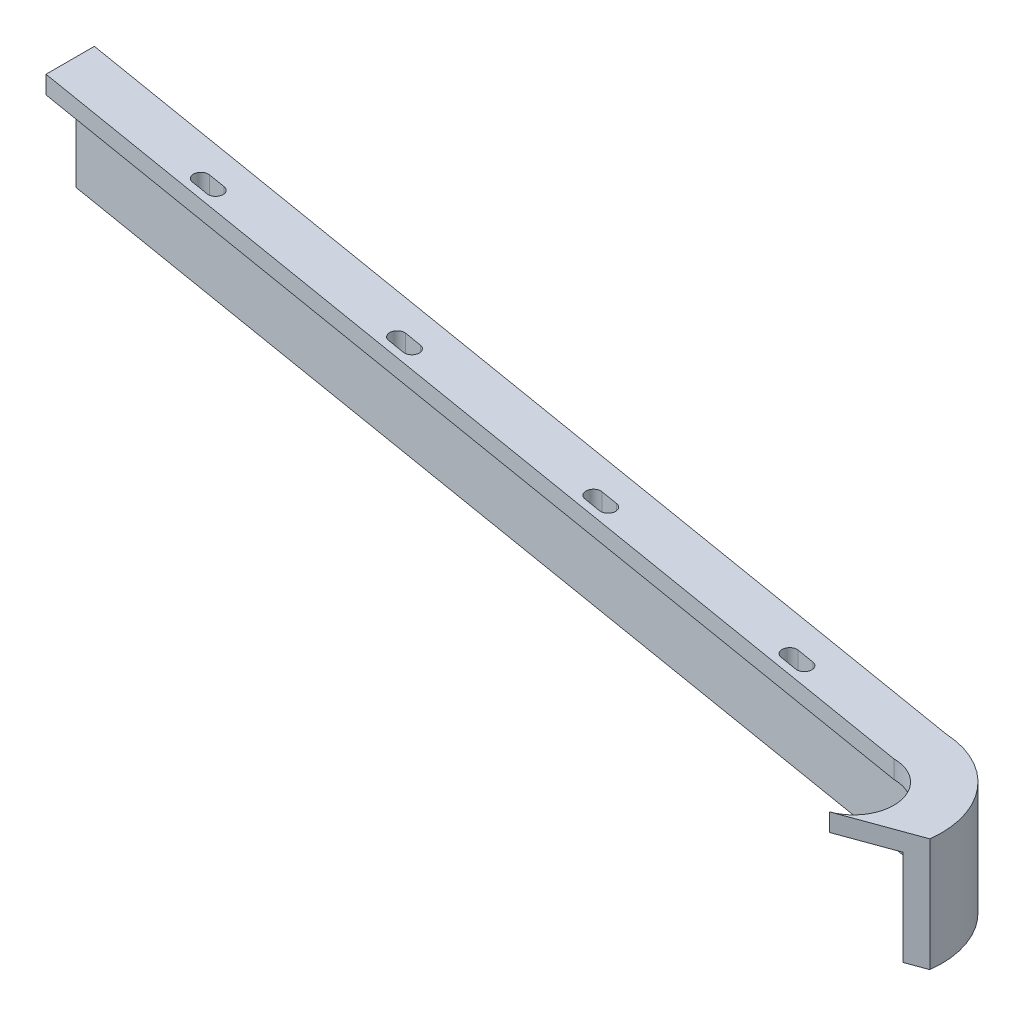
SolidWorks part; units mm, degrees
ref_plane "前视基准面" through (0, 0, 0) normal (0, 0, 1) x (1, 0, 0)
ref_plane "上视基准面" through (0, 0, 0) normal (0, 1, 0) x (1, 0, 0)
ref_plane "右视基准面" through (0, 0, 0) normal (1, 0, 0) x (0, 0, -1)
sketch "草图1" plane through (0, 0, 0) normal (0, 1, 0) x (1, 0, 0)
  line L1 (-17.5, -27.5) -> (17.5, -27.5)
  line L2 (-17.5, -27.5) -> (-17.5, 27.5)
  line L3 (-17.5, 27.5) -> (17.5, 27.5)
  line L4 (17.5, -27.5) -> (17.5, 27.5)
  line L5 (-17.5, -27.5) -> (17.5, 27.5) construction
  line L6 (-17.5, 27.5) -> (17.5, -27.5) construction
  point P0 (0, 0)
  dimension "D1" = 55
  dimension "D2" = 35
extrude "凸台-拉伸1" add sketch "草图1" along normal blind 1
sketch "草图2" plane through (0, 1, 0) normal (0, 1, 0) x (1, 0, 0)
  line L0 (-105.917, 0) -> (-62.25, 0) construction
  line L1 (106.75, 2.25) -> (121.75, 2.25)
  line L2 (-31.4474, 57.1013) -> (151.75, 26.6691)
  line L4 (124.0586, 2.6571) -> (154.0586, 13.5762)
  line L5 (-60.1618, 23.6059) -> (-42.6093, 52.0296)
  line L6 (121.75, 2.25) -> (121.75, 9) construction
  line L7 (121.75, -2.25) -> (121.75, -9) construction
  line L8 (-60.1618, -23.6059) -> (-42.6093, -52.0296)
  line L9 (124.0586, -2.6571) -> (154.0586, -13.5762)
  line L10 (121.75, -9) -> (128.5, -9)
  line L11 (-31.4474, -57.1013) -> (151.75, -26.6691)
  line L12 (106.75, -2.25) -> (121.75, -2.25)
  line L13 (-62.25, 16.25) -> (-62.25, -16.25)
  line L14 (106.75, 2.25) -> (106.75, -2.25)
  line L15 (106.75, 0) -> (124.0666, 0) construction
  arc A0 (-60.1618, 23.6059) -> (-62.25, 16.25) centre (-48.25, 16.25) ccw
  arc A1 (-31.4474, 57.1013) -> (-42.6093, 52.0296) centre (-33.25, 46.25) ccw
  arc A2 (121.75, 2.25) -> (124.0586, 2.6571) centre (121.75, 9) ccw
  arc A3 (154.0586, 13.5762) -> (151.75, 26.6691) centre (151.75, 19.9191) ccw
  arc A4 (154.0586, -13.5762) -> (151.75, -26.6691) centre (151.75, -19.9191) cw
  arc A5 (121.75, -2.25) -> (128.5, -9) centre (121.75, -9) cw
  arc A6 (-31.4474, -57.1013) -> (-42.6093, -52.0296) centre (-33.25, -46.25) cw
  arc A7 (-60.1618, -23.6059) -> (-62.25, -16.25) centre (-48.25, -16.25) cw
  line M10 (17.5, -27.5) -> (17.5, 27.5)
  line M11 (17.5, 27.5) -> (-17.5, 27.5)
  line M12 (-17.5, 27.5) -> (-17.5, -27.5)
  line M13 (-17.5, -27.5) -> (17.5, -27.5)
  dimension "D2" = 28
  dimension "D3" = 48.25
  dimension "D4" = 22
  dimension "D5" = 15
  dimension "D7" = 13.5
  dimension "D10" = 13.5
  dimension "D11" = 30
  dimension "D1" = 2.25
  dimension "D8" = 20
  dimension "D9" = 30
  dimension "D12" = 15
extrude "凸台-拉伸2" add sketch "草图2" along normal blind 3 contours A7 L8 A6 L11 A4 L9 A5 L12 L14 L1 A2 L4 A3 L2 A1 L5 A0 L13 | M13 M10 M11 M12 region at (37.3678, 1, 0) region at (0, 1, 0)
sketch "草图3" plane through (0, 4, 0) normal (0, 1, 0) x (1, 0, 0)
  circle A0 centre (-48.25, 16.25) radius 5
  circle A1 centre (-48.25, -16.25) radius 5
  circle A2 centre (-33.25, 46.25) radius 6.6982
  circle A3 centre (151.75, 19.9191) radius 2.5794
  circle A4 centre (121.75, 9) radius 2.5794
  circle A5 centre (121.75, -9) radius 2.5794
  circle A6 centre (151.75, -19.9191) radius 2.5794
  circle A7 centre (-33.25, -46.25) radius 6.6982
  dimension "D1" = 10
extrude "切除-拉伸1" cut sketch "草图3" against normal through all contours A0 | A1 region at (-48.25, 4, -16.25)
sketch "草图4" plane through (0, 4, 0) normal (0, 1, 0) x (1, 0, 0)
  circle A0 centre (-33.25, 46.25) radius 4
  circle A1 centre (-33.25, -46.25) radius 4
  dimension "D1" = 8
  dimension "D2" = 8
extrude "切除-拉伸2" cut sketch "草图4" against normal blind 2
sketch "草图5" plane through (0, 4, 0) normal (0, 1, 0) x (1, 0, 0)
  circle A0 centre (121.75, 9) radius 2
  circle A1 centre (121.75, -9) radius 2
  circle A2 centre (151.75, 19.9191) radius 2
  circle A3 centre (151.75, -19.9191) radius 2
  dimension "D1" = 4
extrude "切除-拉伸3" cut sketch "草图5" against normal blind 2
sketch "草图8" plane through (0, 1, 0) normal (0, -1, 0) x (1, 0, 0)
  line L1 (-39.75, -26.25) -> (-26.75, -26.25)
  line L2 (-39.75, -26.25) -> (-39.75, -66.25)
  line L3 (-39.75, -66.25) -> (-26.75, -66.25)
  line L4 (-26.75, -26.25) -> (-26.75, -66.25)
  line L5 (-39.75, -26.25) -> (-26.75, -66.25) construction
  line L6 (-39.75, -66.25) -> (-26.75, -26.25) construction
  line L16 (124.0586, 2.6571) -> (154.0586, 13.5762)
  line L17 (151.75, 26.6691) -> (-31.4474, 57.1013)
  line L18 (-42.6093, 52.0296) -> (-60.1618, 23.6059)
  line L19 (-62.25, 16.25) -> (-62.25, -16.25)
  line L20 (-60.1618, -23.6059) -> (-42.6093, -52.0296)
  line L21 (-31.4474, -57.1013) -> (151.75, -26.6691)
  line L22 (154.0586, -13.5762) -> (124.0586, -2.6571)
  line L23 (121.75, -2.25) -> (106.75, -2.25)
  line L24 (106.75, -2.25) -> (106.75, 2.25)
  line L25 (106.75, 2.25) -> (121.75, 2.25)
  line L26 (124.0586, 2.6571) -> (154.0586, 13.5762)
  line L27 (151.75, 26.6691) -> (-31.4474, 57.1013)
  line L28 (-42.6093, 52.0296) -> (-60.1618, 23.6059)
  line L31 (-31.4474, -57.1013) -> (151.75, -26.6691)
  line L32 (154.0586, -13.5762) -> (124.0586, -2.6571)
  line L33 (121.75, -2.25) -> (106.75, -2.25)
  line L34 (106.75, -2.25) -> (106.75, 2.25)
  line L35 (106.75, 2.25) -> (121.75, 2.25)
  arc A8 (154.0586, 13.5762) -> (151.75, 26.6691) centre (151.75, 19.9191) ccw
  arc A9 (-31.4474, 57.1013) -> (-42.6093, 52.0296) centre (-33.25, 46.25) ccw
  arc A10 (-60.1618, 23.6059) -> (-62.25, 16.25) centre (-48.25, 16.25) ccw
  arc A11 (-62.25, -16.25) -> (-60.1618, -23.6059) centre (-48.25, -16.25) ccw
  arc A12 (-42.6093, -52.0296) -> (-31.4474, -57.1013) centre (-33.25, -46.25) ccw
  arc A13 (151.75, -26.6691) -> (154.0586, -13.5762) centre (151.75, -19.9191) ccw
  arc A14 (124.0586, -2.6571) -> (121.75, -2.25) centre (121.75, -9) ccw
  arc A15 (121.75, 2.25) -> (124.0586, 2.6571) centre (121.75, 9) ccw
  arc A16 (154.0586, 13.5762) -> (151.75, 26.6691) centre (151.75, 19.9191) ccw
  arc A17 (-31.4474, 57.1013) -> (-42.6093, 52.0296) centre (-33.25, 46.25) ccw
  arc A18 (-60.1618, 23.6059) -> (-62.25, 16.25) centre (-48.25, 16.25) ccw
  arc A19 (-62.25, -16.25) -> (-60.1618, -23.6059) centre (-48.25, -16.25) ccw
  arc A20 (-42.6093, -52.0296) -> (-31.4474, -57.1013) centre (-33.25, -46.25) ccw
  arc A21 (151.75, -26.6691) -> (154.0586, -13.5762) centre (151.75, -19.9191) ccw
  arc A22 (124.0586, -2.6571) -> (121.75, -2.25) centre (121.75, -9) ccw
  arc A23 (121.75, 2.25) -> (124.0586, 2.6571) centre (121.75, 9) ccw
  point P0 (-33.25, -46.25)
  arc M32 (-42.6093, -52.0296) -> (-31.4474, -57.1013) centre (-33.25, -46.25) ccw
  line M33 (-31.4474, -57.1013) -> (151.75, -26.6691)
  dimension "D1" = 13
  dimension "D2" = 40
  dimension "D3" = 0
extrude "凸台-拉伸3" add sketch "草图8" along normal blind 7 contours L4 L1 L2 M32 M33 region at (-33.2258, 1, -41.4837)
mirror "镜向1" about plane through (0, 0, 0) normal (0, 0, 1) of "凸台-拉伸3"
sketch "草图9" plane through (0, -6, 0) normal (0, -1, 0) x (1, 0, 0)
  line L0 (-39.75, -26.25) -> (-26.75, -26.25) construction
  line L2 (-38.25, -53.75) -> (-38.25, -27.75)
  line L3 (-38.25, -27.75) -> (-28.25, -27.75)
  line L4 (-28.25, -53.75) -> (-28.25, -27.75)
  line L5 (-35.5448, -54.7408) -> (-28.25, -27.75) construction
  line L6 (-38.25, -27.75) -> (-31.223, -53.75) construction
  line L8 (-28.25, -53.75) -> (-38.25, -53.75)
  point P0 (-33.25, -46.25)
  dimension "D1" = 10
  dimension "D2" = 1.5
  dimension "D3" = 26
extrude "切除-拉伸4" cut sketch "草图9" against normal through all from offset 1.5 offset against normal yes
mirror "镜向2" about plane through (0, 0, 0) normal (0, 0, 1) of "切除-拉伸4"
sketch "草图10" plane through (0, 0, -53.75) normal (0, 0, 1) x (1, 0, 0)
  line L4 (-38.25, -4.5) -> (-28.25, -4.5)
  line L5 (-28.25, -4.5) -> (-28.25, 4)
  line L6 (-28.25, 4) -> (-38.25, 4)
  line L7 (-38.25, 4) -> (-38.25, -4.5)
  line L8 (-38.25, -4.5) -> (-28.25, -4.5)
  line L9 (-28.25, -4.5) -> (-28.25, 4)
  line L10 (-28.25, 4) -> (-38.25, 4)
  line L11 (-38.25, 4) -> (-38.25, -4.5)
  circle A0 centre (-33.25, -1.5) radius 1.5
  dimension "D2" = 3
  dimension "D3" = 3
  dimension "D1" = 0
extrude "切除-拉伸5" cut sketch "草图10" against normal through all contours A0 region at (-33.25, -1.5, -53.75)
mirror "镜向3" about plane through (0, 0, 0) normal (0, 0, 1) of "切除-拉伸5"
sketch "草图12" plane through (0, 4, 0) normal (0, 1, 0) x (1, 0, 0)
  line L3 (152.5362, 34.6481) -> (-30.1364, 64.9932)
  line L5 (-42.6093, 52.0296) -> (-60.1618, 23.6059) construction
  line L6 (124.0586, 2.6571) -> (154.0586, 13.5762) construction
  line L10 (154.0586, -13.5762) -> (124.0586, -2.6571)
  line L11 (121.75, -2.25) -> (106.75, -2.25)
  line L12 (106.75, -2.25) -> (106.75, 2.25)
  line L13 (106.75, 2.25) -> (121.75, 2.25)
  line L14 (124.0586, 2.6571) -> (154.0586, 13.5762)
  line L15 (151.75, 26.6691) -> (-31.4474, 57.1013)
  line L16 (-42.6093, 52.0296) -> (-60.1618, 23.6059)
  line L17 (-62.25, 16.25) -> (-62.25, -16.25)
  line L18 (-60.1618, -23.6059) -> (-42.6093, -52.0296)
  line L19 (-31.4474, -57.1013) -> (151.75, -26.6691)
  line L23 (-62.25, 2.25) -> (121.75, 2.25)
  line L24 (124.0586, 2.6571) -> (166.3826, 18.0617)
  line L26 (-34.4695, 65.2108) -> (-60.1618, 23.6059)
  line L27 (-62.25, 16.25) -> (-62.25, 2.25)
  line L30 (-49.416, 56.233) -> (-66.9685, 27.8093) construction
  line L31 (-70.25, 16.25) -> (-70.25, -5.75) construction
  line L32 (-70.25, -5.75) -> (121.75, -5.75) construction
  line L33 (126.7948, -4.8605) -> (156.7948, 6.0586) construction
  line L34 (151.75, 26.6691) -> (-31.4474, 57.1013) construction
  arc A1 (166.3826, 18.0617) -> (152.5362, 34.6481) centre (151.75, 19.9191) ccw
  arc A2 (-30.1364, 64.9932) -> (-34.4695, 65.2108) centre (-33.25, 46.25) ccw
  arc A4 (-30.1364, 64.9932) -> (-49.416, 56.233) centre (-33.25, 46.25) ccw construction
  arc A5 (156.7948, 6.0586) -> (152.5362, 34.6481) centre (151.75, 19.9191) ccw construction
  arc A8 (124.0586, -2.6571) -> (121.75, -2.25) centre (121.75, -9) ccw
  arc A9 (121.75, 2.25) -> (124.0586, 2.6571) centre (121.75, 9) ccw
  arc A10 (154.0586, 13.5762) -> (151.75, 26.6691) centre (151.75, 19.9191) ccw
  arc A11 (-31.4474, 57.1013) -> (-42.6093, 52.0296) centre (-33.25, 46.25) ccw
  arc A12 (-60.1618, 23.6059) -> (-62.25, 16.25) centre (-48.25, 16.25) ccw
  arc A13 (-62.25, -16.25) -> (-60.1618, -23.6059) centre (-48.25, -16.25) ccw
  arc A14 (-42.6093, -52.0296) -> (-31.4474, -57.1013) centre (-33.25, -46.25) ccw
  arc A15 (151.75, -26.6691) -> (154.0586, -13.5762) centre (151.75, -19.9191) ccw
  arc A17 (121.75, 2.25) -> (124.0586, 2.6571) centre (121.75, 9) ccw
  arc A20 (-60.1618, 23.6059) -> (-62.25, 16.25) centre (-48.25, 16.25) ccw
  arc A24 (-66.9685, 27.8093) -> (-70.25, 16.25) centre (-48.25, 16.25) ccw construction
  arc A25 (121.75, -5.75) -> (126.7948, -4.8605) centre (121.75, 9) ccw construction
  arc A26 (-31.4474, 57.1013) -> (-42.6093, 52.0296) centre (-33.25, 46.25) ccw construction
  arc A27 (154.0586, 13.5762) -> (151.75, 26.6691) centre (151.75, 19.9191) ccw construction
  dimension "D1" = 0
  dimension "D2" = 8
extrude "凸台-拉伸4" add sketch "草图12" along normal blind 3
sketch "草图13" plane through (0, 4, 0) normal (0, -1, 0) x (1, 0, 0)
  line L1 (-119.1699, 86.8947) -> (214.8426, 86.8947)
  line L2 (-119.1699, 86.8947) -> (-119.1699, -74.5615)
  line L3 (-119.1699, -74.5615) -> (214.8426, -74.5615)
  line L4 (214.8426, 86.8947) -> (214.8426, -74.5615)
  line L5 (-119.1699, 86.8947) -> (214.8426, -74.5615) construction
  line L6 (-119.1699, -74.5615) -> (214.8426, 86.8947) construction
  point P0 (47.8363, 6.1666)
extrude "切除-拉伸6" cut sketch "草图13" along normal blind 10
sketch "草图14" plane through (0, 4, 0) normal (0, -1, 0) x (1, 0, 0)
  circle A0 centre (151.75, -19.9191) radius 3.5
  circle A1 centre (121.75, -9) radius 3.5
  dimension "D2" = 7
  dimension "D3" = 7
extrude "切除-拉伸7" cut sketch "草图14" against normal blind 2.5
sketch "草图15" plane through (0, 4, 0) normal (0, -1, 0) x (1, 0, 0)
  circle A0 centre (-48.25, -16.25) radius 5
  dimension "D1" = 10
extrude "切除-拉伸8" cut sketch "草图15" against normal through all
sketch "草图17" plane through (0, 4, 0) normal (0, -1, 0) x (1, 0, 0)
  line L0 (-30.6281, -62.0337) -> (152.2188, -31.6598)
  line L1 (-34.4695, -65.2108) -> (-36.5044, -61.9155)
  line L3 (166.3826, -18.0617) -> (163.0963, -16.8656)
  line L5 (166.3826, -18.0617) -> (124.0586, -2.6571)
  line L6 (121.75, -2.25) -> (-62.25, -2.25)
  line L7 (-62.25, -2.25) -> (-62.25, -16.25)
  line L8 (-60.1618, -23.6059) -> (-34.4695, -65.2108)
  line L9 (-30.1364, -64.9932) -> (152.5362, -34.6481)
  line L14 (-30.1364, -64.9932) -> (152.5362, -34.6481)
  arc A0 (-36.5044, -61.9155) -> (-30.6281, -62.0337) centre (-33.25, -46.25) ccw
  arc A1 (152.2188, -31.6598) -> (163.0963, -16.8656) centre (151.75, -19.9191) ccw
  arc A2 (-34.2769, -62.217) -> (-30.6281, -62.0337) centre (-33.25, -46.25) ccw construction
  arc A3 (152.2188, -31.6598) -> (163.4065, -18.4395) centre (151.75, -19.9191) ccw construction
  arc A4 (124.0586, -2.6571) -> (121.75, -2.25) centre (121.75, -9) ccw
  arc A5 (-62.25, -16.25) -> (-60.1618, -23.6059) centre (-48.25, -16.25) ccw
  arc A6 (-34.4695, -65.2108) -> (-30.1364, -64.9932) centre (-33.25, -46.25) ccw
  arc A7 (152.5362, -34.6481) -> (166.3826, -18.0617) centre (151.75, -19.9191) ccw
  arc A10 (-34.4695, -65.2108) -> (-30.1364, -64.9932) centre (-33.25, -46.25) ccw
  arc A11 (152.5362, -34.6481) -> (166.3826, -18.0617) centre (151.75, -19.9191) ccw
  dimension "D1" = 0
  dimension "D2" = 3
extrude "凸台-拉伸5" add sketch "草图17" along normal blind 16
sketch "草图18" plane through (0, 7, 0) normal (0, 1, 0) x (1, 0, 0)
  line L1 (-39.75, 26.25) -> (-26.75, 26.25)
  line L2 (-39.75, 26.25) -> (-39.75, 56.6598)
  line L4 (-26.75, 26.25) -> (-26.75, 64.4306)
  line L5 (-39.75, 26.25) -> (-27.311, 64.5238) construction
  line L6 (-37.7079, 59.9667) -> (-26.75, 26.25) construction
  line L11 (-62.25, 16.25) -> (-62.25, 2.25)
  line L12 (-62.25, 2.25) -> (121.75, 2.25)
  line L13 (124.0586, 2.6571) -> (166.3826, 18.0617)
  line L14 (152.5362, 34.6481) -> (-30.1364, 64.9932)
  line L15 (-34.4695, 65.2108) -> (-60.1618, 23.6059)
  line L19 (-26.75, 64.4306) -> (-30.1364, 64.9932)
  line L20 (-34.4695, 65.2108) -> (-39.75, 56.6598)
  arc A0 (-30.1364, 64.9932) -> (-34.4695, 65.2108) centre (-33.25, 46.25) ccw construction
  arc A1 (-30.1364, 64.9932) -> (-34.4695, 65.2108) centre (-33.25, 46.25) ccw
  arc A6 (121.75, 2.25) -> (124.0586, 2.6571) centre (121.75, 9) ccw
  arc A7 (166.3826, 18.0617) -> (152.5362, 34.6481) centre (151.75, 19.9191) ccw
  arc A8 (-30.1364, 64.9932) -> (-34.4695, 65.2108) centre (-33.25, 46.25) ccw
  arc A9 (-60.1618, 23.6059) -> (-62.25, 16.25) centre (-48.25, 16.25) ccw
  arc A10 (121.75, 2.25) -> (124.0586, 2.6571) centre (121.75, 9) ccw
  arc A12 (-30.1364, 64.9932) -> (-34.4695, 65.2108) centre (-33.25, 46.25) ccw
  line M18 (152.5362, 34.6481) -> (-30.1364, 64.9932)
  arc M19 (-30.1364, 64.9932) -> (-34.4695, 65.2108) centre (-33.25, 46.25) ccw
  line M20 (-34.4695, 65.2108) -> (-60.1618, 23.6059)
  dimension "D3" = 0
extrude "凸台-拉伸6" add sketch "草图18" along normal blind 7 contours L1 L4 L2 M18 M19 M20 region at (-33.0469, 7, -44.8798)
sketch "草图19" plane through (0, 14, 0) normal (0, 1, 0) x (1, 0, 0)
  line L5 (-38.25, 53.75) -> (-28.25, 53.75)
  line L8 (-38.25, 27.75) -> (-28.25, 27.75)
  line L9 (-28.25, 64.75) -> (-28.25, 64.6798)
  line L10 (-39.75, 26.25) -> (-26.75, 26.25)
  line L11 (-26.75, 26.25) -> (-26.75, 64.4306)
  line L12 (-26.75, 64.4306) -> (-30.1364, 64.9932)
  line L13 (-34.4695, 65.2108) -> (-39.75, 56.6598)
  line L14 (-39.75, 56.6598) -> (-39.75, 26.25)
  line L17 (-26.75, 64.4306) -> (-28.6727, 64.75)
  line L18 (-34.4695, 65.2108) -> (-34.754, 64.75)
  line L21 (-38.25, 27.75) -> (-31.223, 53.75) construction
  line L22 (-38.25, 53.75) -> (-38.25, 27.75)
  line L23 (-35.277, 53.75) -> (-28.25, 27.75) construction
  line L24 (-28.2682, 64.6828) -> (-28.25, 64.75) construction
  line L25 (-28.25, 53.75) -> (-28.25, 27.75)
  line L27 (-28.6727, 64.75) -> (-28.25, 64.75)
  arc A2 (-30.1364, 64.9932) -> (-34.4695, 65.2108) centre (-33.25, 46.25) ccw
  dimension "D2" = 10
  dimension "D4" = 26
  dimension "D1" = 0
extrude "切除-拉伸9" cut sketch "草图19" against normal through all from offset 1.5 contours L25 L5 L22 L8 region at (-33.25, 14, -40.75) offset against normal yes
sketch "草图20" plane through (0, 0, -53.75) normal (0, 0, 1) x (1, 0, 0)
  line L4 (-38.25, 4) -> (-28.25, 4)
  line L5 (-28.25, 4) -> (-28.25, 12.5)
  line L6 (-28.25, 12.5) -> (-38.25, 12.5)
  line L7 (-38.25, 12.5) -> (-38.25, 4)
  line L8 (-38.25, 4) -> (-28.25, 4)
  line L9 (-28.25, 4) -> (-28.25, 12.5)
  line L10 (-28.25, 12.5) -> (-38.25, 12.5)
  line L11 (-38.25, 12.5) -> (-38.25, 4)
  circle A0 centre (-33.25, 9.5) radius 1.5
  dimension "D2" = 3
  dimension "D3" = 3
  dimension "D1" = 0
extrude "切除-拉伸10" cut sketch "草图20" against normal through all contours A0 region at (-33.25, 9.5, -53.75)
thread "螺纹线1" pitch 0.6 method cut profile "螺纹线轮廓1" start angle 0, offset 0, length 15, pitch 0.6, diameter 3
ref_plane "基准面1" through (-34.75, 9.5, -53.75) normal (0, -1, 0) x (-1, 0, 0)
sketch "螺纹线轮廓1" plane through (-34.75, 9.5, -53.75) normal (0, -1, 0) x (-1, 0, 0)
  line L0 (0, 0) -> (0, 0.6) construction
  line L1 (0, 0) -> (0.3248, 0.1875)
  line L2 (0.3248, 0.1875) -> (0.3248, 0.2625)
  line L3 (0.3248, 0.2625) -> (0, 0.45)
  line L4 (0.3248, 0.225) -> (0, 0.225) construction
  line L11 (0, 0) -> (0, 0.45)
  point P2 (0, 0)
  dimension "Pitch" = 0.6
  dimension "Profile_Angle" = 60
  dimension "Profile_Land" = 0.075
  dimension "Profile_Height" = 0.3248
sketch "草图21" plane through (0, 14, 0) normal (0, 1, 0) x (1, 0, 0)
  line L0 (-38.25, 27.75) -> (-28.25, 27.75) construction
  line L1 (-39.75, 27.75) -> (-26.75, 27.75)
  line L5 (-39.75, 26.25) -> (-26.75, 26.25)
  line L6 (-26.75, 26.25) -> (-26.75, 64.4306)
  line L7 (-26.75, 64.4306) -> (-30.1364, 64.9932)
  line L8 (-34.4695, 65.2108) -> (-39.75, 56.6598)
  line L9 (-39.75, 56.6598) -> (-39.75, 26.25)
  line L11 (-26.75, 27.75) -> (-26.75, 64.4306)
  line L12 (-26.75, 64.4306) -> (-30.1364, 64.9932)
  line L13 (-34.4695, 65.2108) -> (-39.75, 56.6598)
  line L14 (-39.75, 56.6598) -> (-39.75, 27.75)
  arc A1 (-30.1364, 64.9932) -> (-34.4695, 65.2108) centre (-33.25, 46.25) ccw
  arc A2 (-30.1364, 64.9932) -> (-34.4695, 65.2108) centre (-33.25, 46.25) ccw
  dimension "D1" = 0
extrude "切除-拉伸11" cut sketch "草图21" against normal through all
sketch "草图22" plane through (0, 14, 0) normal (0, 1, 0) x (1, 0, 0)
  line L4 (-26.75, 27.75) -> (-39.75, 27.75)
  line L5 (-39.75, 27.75) -> (-39.75, 26.25)
  line L6 (-39.75, 26.25) -> (-26.75, 26.25)
  line L7 (-26.75, 26.25) -> (-26.75, 27.75)
  line L8 (-26.75, 27.75) -> (-39.75, 27.75)
  line L9 (-39.75, 27.75) -> (-39.75, 26.25)
  line L10 (-39.75, 26.25) -> (-26.75, 26.25)
  line L11 (-26.75, 26.25) -> (-26.75, 27.75)
  dimension "D1" = 0
extrude "切除-拉伸12" cut sketch "草图22" against normal up to surface (7 mm away) up to face at (-48.25, 7, -21.25)
sketch "草图23" plane through (0, 7, 0) normal (0, 1, 0) x (1, 0, 0)
  line L0 (-45.75, 27.75) -> (-20.75, 27.75)
  line L1 (-20.75, 27.75) -> (-18.75, 27.75)
  line L2 (-18.75, 63.1017) -> (-18.75, 2.25)
  line L8 (-26.75, 64.4306) -> (-26.75, 27.75)
  line L9 (-26.75, 27.75) -> (-39.75, 27.75)
  line L10 (-39.75, 27.75) -> (-39.75, 56.6598)
  line L11 (-39.75, 56.6598) -> (-60.1618, 23.6059)
  line L12 (-62.25, 16.25) -> (-62.25, 2.25)
  line L13 (-62.25, 2.25) -> (121.75, 2.25)
  line L14 (124.0586, 2.6571) -> (166.3826, 18.0617)
  line L15 (152.5362, 34.6481) -> (-26.75, 64.4306)
  line L16 (-26.75, 64.4306) -> (-26.75, 27.75)
  line L17 (-26.75, 27.75) -> (-39.75, 27.75)
  line L18 (-39.75, 27.75) -> (-39.75, 56.6598)
  line L19 (-39.75, 56.6598) -> (-60.1618, 23.6059)
  line L20 (-62.25, 16.25) -> (-62.25, 2.25)
  line L21 (-62.25, 2.25) -> (-18.75, 2.25)
  line L23 (-18.75, 63.1017) -> (-26.75, 64.4306)
  circle A0 centre (-48.25, 16.25) radius 5 construction
  circle A1 centre (-48.25, 16.25) radius 5
  arc A3 (-60.1618, 23.6059) -> (-62.25, 16.25) centre (-48.25, 16.25) ccw
  arc A4 (121.75, 2.25) -> (124.0586, 2.6571) centre (121.75, 9) ccw
  arc A5 (166.3826, 18.0617) -> (152.5362, 34.6481) centre (151.75, 19.9191) ccw
  arc A6 (-60.1618, 23.6059) -> (-62.25, 16.25) centre (-48.25, 16.25) ccw
  point P13 (-33.25, 27.75)
  line M14 (-26.75, 64.4306) -> (-26.75, 27.75)
  line M15 (-26.75, 27.75) -> (-39.75, 27.75)
  line M16 (-39.75, 27.75) -> (-39.75, 56.6598)
  line M17 (-39.75, 56.6598) -> (-60.1618, 23.6059)
  arc M18 (-60.1618, 23.6059) -> (-62.25, 16.25) centre (-48.25, 16.25) ccw
  line M19 (-62.25, 16.25) -> (-62.25, 2.25)
  line M20 (-62.25, 2.25) -> (121.75, 2.25)
  line M24 (152.5362, 34.6481) -> (-26.75, 64.4306)
  circle M25 centre (-48.25, 16.25) radius 5
  dimension "D2" = 25
  dimension "D3" = 2
  dimension "D1" = 0
extrude "凸台-拉伸7" add sketch "草图23" along normal blind 2 contours L2 L1 L0 M15 M16 M17 M18 M19 M20 M25 | L2 L0 L1 M24 M14 region at (-40.7754, 7, -19.3253) region at (-22.7746, 7, -45.7601)
sketch "草图24" plane through (0, 9, 0) normal (0, 1, 0) x (1, 0, 0)
  line L0 (-45.75, 27.75) -> (-20.75, 27.75)
  line L1 (-45.75, 27.75) -> (-45.75, 46.9437)
  line L2 (-39.75, 56.6598) -> (-60.1618, 23.6059) construction
  line L3 (-20.75, 27.75) -> (-20.75, 86.4202)
  line L4 (-20.75, 86.4202) -> (-45.75, 86.4202)
  line L5 (-45.75, 86.4202) -> (-45.75, 46.0349)
  point P3 (-33.25, 27.75)
  line M3 (-39.75, 27.75) -> (-39.75, 56.6598)
  line M4 (-39.75, 56.6598) -> (-60.1618, 23.6059)
  line M9 (-18.75, 63.1017) -> (-26.75, 64.4306)
  line M10 (-26.75, 64.4306) -> (-26.75, 27.75)
  dimension "D1" = 25
extrude "切除-拉伸15" cut sketch "草图24" against normal through all from offset 3 contours L1 L0 M3 M4 | L0 L3 M9 M10 region at (-42.548, 9, -39.9394) region at (-23.7638, 9, -45.8423) offset against normal yes
sketch "草图25" plane through (0, 4, 0) normal (0, -1, 0) x (1, 0, 0)
  circle A0 centre (-48.25, -16.25) radius 7.5
  dimension "D1" = 15
extrude "切除-拉伸16" cut sketch "草图25" against normal blind 4
sketch "草图26" plane through (0, 7, 0) normal (0, 1, 0) x (1, 0, 0)
  line L0 (-48.25, 16.25) -> (51.3855, 16.25)
  line L1 (1.75, 16.25) -> (5.75, 16.25) construction
  line L2 (1.75, 18) -> (5.75, 18)
  line L3 (1.75, 14.5) -> (5.75, 14.5)
  line L4 (41.75, 16.25) -> (45.75, 16.25) construction
  line L5 (41.75, 18) -> (45.75, 18)
  line L6 (41.75, 14.5) -> (45.75, 14.5)
  line L7 (81.75, 16.25) -> (85.75, 16.25) construction
  line L8 (81.75, 18) -> (85.75, 18)
  line L9 (81.75, 14.5) -> (85.75, 14.5)
  line L10 (1.75, 31.25) -> (1.75, 35.25) construction
  line L11 (0, 31.25) -> (0, 35.25)
  line L12 (3.5, 31.25) -> (3.5, 35.25)
  arc A0 (1.75, 18) -> (1.75, 14.5) centre (1.75, 16.25) ccw
  arc A1 (5.75, 14.5) -> (5.75, 18) centre (5.75, 16.25) ccw
  arc A2 (41.75, 18) -> (41.75, 14.5) centre (41.75, 16.25) ccw
  arc A3 (45.75, 14.5) -> (45.75, 18) centre (45.75, 16.25) ccw
  arc A4 (81.75, 18) -> (81.75, 14.5) centre (81.75, 16.25) ccw
  arc A5 (85.75, 14.5) -> (85.75, 18) centre (85.75, 16.25) ccw
  arc A6 (0, 31.25) -> (3.5, 31.25) centre (1.75, 31.25) ccw
  arc A7 (3.5, 35.25) -> (0, 35.25) centre (1.75, 35.25) ccw
  point P5 (3.75, 16.25)
  point P10 (43.75, 16.25)
  point P17 (83.75, 16.25)
  point P24 (3.75, 14.5)
  point P27 (1.75, 33.25)
  dimension "D1" = 3.5
  dimension "D2" = 4
  dimension "D3" = 40
  dimension "D4" = 40
  dimension "D5" = 50
  dimension "D6" = 15
extrude "切除-拉伸17" cut sketch "草图26" against normal blind 10 contours L12 A7 L11 A6 | L0 A3 L5 A2 | L6 A3 L0 A2 | L9 A5 L8 A4 | L2 A1 L3 A0 region at (43.75, 7, -17.0711) region at (43.75, 7, -15.4289) region at (83.75, 7, -16.25) region at (1.75, 7, -33.25)
sketch "草图27" plane through (0, 6, 0) normal (0, -1, 0) x (1, 0, 0)
  line L0 (-26.75, -27.75) -> (-20.75, -27.75)
  line L1 (-45.75, -27.75) -> (-39.75, -27.75)
  line L2 (-45.75, -27.75) -> (-39.75, -27.75) construction
  circle A0 centre (-23.75, -32.75) radius 1.75
  circle A1 centre (-23.75, -42.75) radius 1.75
  circle A2 centre (-42.75, -32.75) radius 1.75
  circle A3 centre (-42.75, -42.75) radius 1.75
  dimension "D1" = 3.5
  dimension "D4" = 10
  dimension "D5" = 10
  dimension "D2" = 5
  dimension "D3" = 5
extrude "切除-拉伸18" cut sketch "草图27" against normal blind 10 contours A2 | A3 | A0 | A1 region at (-23.75, 6, -32.75) region at (-42.75, 6, -32.75) region at (-42.75, 6, -42.75)
sketch "草图28" plane through (0, 9, 0) normal (0, 1, 0) x (1, 0, 0)
  line L8 (-26.75, 27.75) -> (-39.75, 27.75)
  line L9 (-39.75, 27.75) -> (-39.75, 56.6598)
  line L10 (-39.75, 56.6598) -> (-60.1618, 23.6059)
  line L11 (-62.25, 16.25) -> (-62.25, 2.25)
  line L12 (-62.25, 2.25) -> (-18.75, 2.25)
  line L13 (-18.75, 2.25) -> (-18.75, 63.1017)
  line L14 (-18.75, 63.1017) -> (-26.75, 64.4306)
  line L15 (-26.75, 64.4306) -> (-26.75, 27.75)
  line L16 (-26.75, 27.75) -> (-39.75, 27.75)
  line L17 (-39.75, 27.75) -> (-39.75, 56.6598)
  line L18 (-39.75, 56.6598) -> (-60.1618, 23.6059)
  line L19 (-62.25, 16.25) -> (-62.25, 2.25)
  line L20 (-62.25, 2.25) -> (-18.75, 2.25)
  line L21 (-18.75, 2.25) -> (-18.75, 63.1017)
  line L22 (-18.75, 63.1017) -> (-26.75, 64.4306)
  line L23 (-26.75, 64.4306) -> (-26.75, 27.75)
  arc A1 (-60.1618, 23.6059) -> (-62.25, 16.25) centre (-48.25, 16.25) ccw
  arc A2 (-60.1618, 23.6059) -> (-62.25, 16.25) centre (-48.25, 16.25) ccw
  dimension "D1" = 0
extrude "切除-拉伸19" cut sketch "草图28" against normal through all
sketch "草图29" plane through (0, 4, 0) normal (0, -1, 0) x (1, 0, 0)
  line L0 (-18.75, -54.992) -> (151.75, -26.6691)
  line L4 (121.75, -2.25) -> (-18.75, -2.25)
  line L5 (-18.75, -2.25) -> (-18.75, -60.0606)
  line L6 (-18.75, -60.0606) -> (152.2188, -31.6598)
  line L7 (163.0963, -16.8656) -> (124.0586, -2.6571)
  line L8 (121.75, -2.25) -> (-18.75, -2.25)
  line L9 (-18.75, -2.25) -> (-18.75, -60.0606)
  line L10 (-18.75, -60.0606) -> (152.2188, -31.6598)
  line L11 (163.0963, -16.8656) -> (124.0586, -2.6571)
  line L12 (-13.75, -54.1615) -> (151.75, -26.6691) construction
  line L17 (158.4746, -20.5043) -> (122.3485, -7.3555) construction
  line L18 (121.75, -7.25) -> (-13.75, -7.25) construction
  line L19 (-13.75, -7.25) -> (-13.75, -54.1615) construction
  arc A0 (151.75, -26.6691) -> (154.0586, -13.5762) centre (151.75, -19.9191) ccw
  arc A2 (152.2188, -31.6598) -> (163.0963, -16.8656) centre (151.75, -19.9191) ccw
  arc A3 (124.0586, -2.6571) -> (121.75, -2.25) centre (121.75, -9) ccw
  arc A4 (152.2188, -31.6598) -> (163.0963, -16.8656) centre (151.75, -19.9191) ccw
  arc A5 (124.0586, -2.6571) -> (121.75, -2.25) centre (121.75, -9) ccw
  arc A6 (151.75, -26.6691) -> (158.4746, -20.5043) centre (151.75, -19.9191) ccw construction
  arc A9 (122.3485, -7.3555) -> (121.75, -7.25) centre (121.75, -9) ccw construction
  arc M7 (0, -31.25) -> (3.5, -31.25) centre (1.75, -31.25) cw
  line M8 (3.5, -31.25) -> (3.5, -35.25)
  arc M9 (3.5, -35.25) -> (0, -35.25) centre (1.75, -35.25) cw
  line M10 (0, -35.25) -> (0, -31.25)
  line M11 (45.75, -18) -> (41.75, -18)
  arc M12 (41.75, -18) -> (41.75, -14.5) centre (41.75, -16.25) cw
  line M13 (41.75, -14.5) -> (45.75, -14.5)
  arc M14 (45.75, -14.5) -> (45.75, -18) centre (45.75, -16.25) cw
  arc M15 (81.75, -18) -> (81.75, -14.5) centre (81.75, -16.25) cw
  line M16 (81.75, -14.5) -> (85.75, -14.5)
  arc M17 (85.75, -14.5) -> (85.75, -18) centre (85.75, -16.25) cw
  line M18 (85.75, -18) -> (81.75, -18)
  line M19 (5.75, -18) -> (1.75, -18)
  arc M20 (1.75, -18) -> (1.75, -14.5) centre (1.75, -16.25) cw
  line M21 (1.75, -14.5) -> (5.75, -14.5)
  arc M22 (5.75, -14.5) -> (5.75, -18) centre (5.75, -16.25) cw
  circle M23 centre (121.75, -9) radius 3.5
  circle M24 centre (151.75, -19.9191) radius 3.5
  line M25 (121.75, -2.25) -> (-18.75, -2.25)
  line M26 (-18.75, -2.25) -> (-18.75, -60.0606)
  arc M30 (124.0586, -2.6571) -> (121.75, -2.25) centre (121.75, -9) ccw
  dimension "D1" = 0
  dimension "D2" = 5
extrude "切除-拉伸23" cut sketch "草图29" against normal blind 10 contours L0 A0 L11 M30 M25 M26 M24 M23 M22 M19 M20 M21 M18 M15 M16 M17 M14 M11 M12 M13 M10 M7 M8 M9 | M23 | M24 region at (54.4927, 4, -22.9012) region at (121.75, 4, -9) region at (151.75, 4, -19.9191)
sketch "草图30" plane through (0, 4, 0) normal (0, -1, 0) x (1, 0, 0)
  line L1 (9.3647, -52.856) -> (12.3242, -52.3644) construction
  line L2 (151.8091, -29.1935) -> (-19.1597, -57.5944)
  line L3 (151.8091, -29.1935) -> (-18.75, -57.5263)
  line L4 (9.1599, -51.6229) -> (12.1193, -51.1313)
  line L5 (9.5696, -54.0891) -> (12.529, -53.5975)
  line L6 (48.824, -46.3011) -> (51.7834, -45.8095) construction
  line L7 (48.6192, -45.068) -> (51.5786, -44.5764)
  line L8 (49.0288, -47.5342) -> (51.9883, -47.0426)
  line L9 (88.2833, -39.7463) -> (91.2427, -39.2547) construction
  line L10 (88.0784, -38.5132) -> (91.0379, -38.0215)
  line L11 (88.4881, -40.9794) -> (91.4476, -40.4878)
  line L12 (127.7425, -33.1914) -> (130.702, -32.6998) construction
  line L13 (127.5377, -31.9583) -> (130.4971, -31.4667)
  line L14 (127.9474, -34.4245) -> (130.9068, -33.9329)
  line L15 (-18.75, -54.992) -> (-18.75, -60.0606) construction
  line L16 (-18.75, -54.992) -> (-18.75, -60.0606)
  arc A0 (9.1599, -51.6229) -> (9.5696, -54.0891) centre (9.3647, -52.856) ccw
  arc A1 (12.529, -53.5975) -> (12.1193, -51.1313) centre (12.3242, -52.3644) ccw
  arc A2 (48.6192, -45.068) -> (49.0288, -47.5342) centre (48.824, -46.3011) ccw
  arc A3 (51.9883, -47.0426) -> (51.5786, -44.5764) centre (51.7834, -45.8095) ccw
  arc A4 (88.0784, -38.5132) -> (88.4881, -40.9794) centre (88.2833, -39.7463) ccw
  arc A5 (91.4476, -40.4878) -> (91.0379, -38.0215) centre (91.2427, -39.2547) ccw
  arc A6 (127.5377, -31.9583) -> (127.9474, -34.4245) centre (127.7425, -33.1914) ccw
  arc A7 (130.9068, -33.9329) -> (130.4971, -31.4667) centre (130.702, -32.6998) ccw
  point P2 (10.8445, -52.6102)
  point P9 (10.6396, -51.3771)
  point P12 (50.3037, -46.0553)
  point P17 (89.763, -39.5005)
  point P26 (129.2223, -32.9456)
  point P31 (0, 0)
  dimension "D2" = 2.5
  dimension "D3" = 3
  dimension "D4" = 40
  dimension "D5" = 40
  dimension "D6" = 40
  dimension "D7" = 30
  dimension "D1" = 2.5
extrude "切除-拉伸24" cut sketch "草图30" against normal blind 10 contours L5 A1 L4 A0 | L8 A3 L7 A2 | L11 A5 L10 A4 | L14 A7 L13 A6
